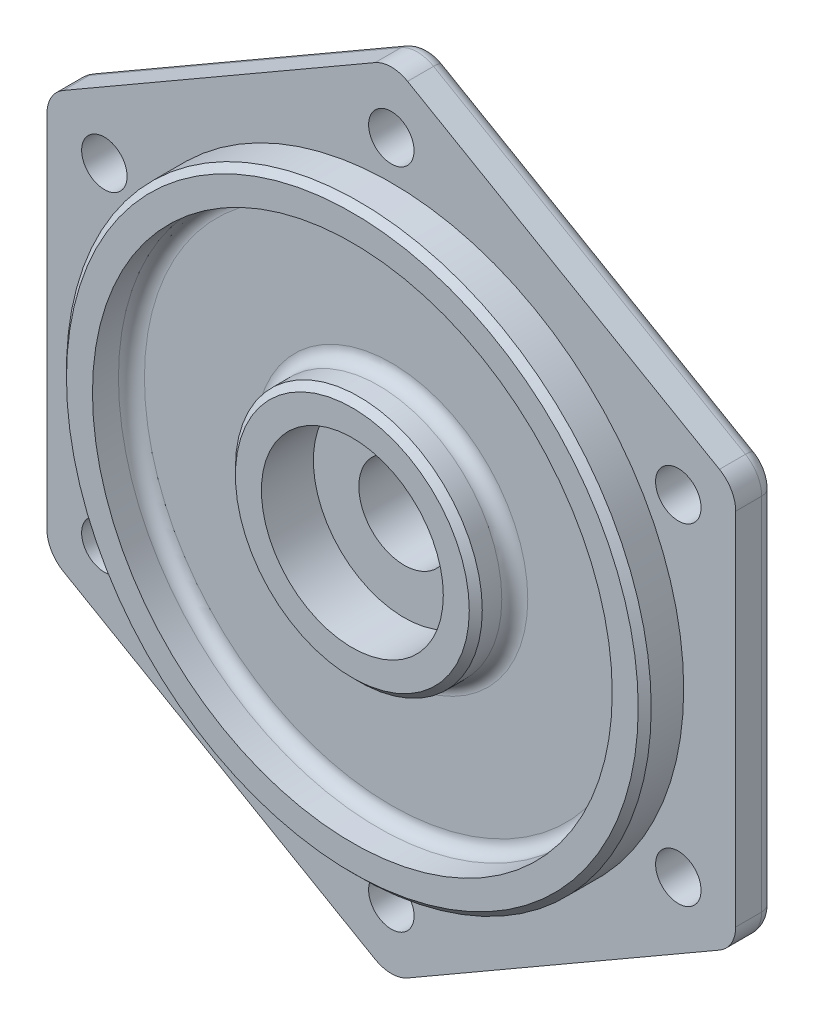
SolidWorks part; units mm, degrees
ref_plane "Front Plane" through (0, 0, 0) normal (0, 0, 1) x (1, 0, 0)
ref_plane "Top Plane" through (0, 0, 0) normal (0, 1, 0) x (1, 0, 0)
ref_plane "Right Plane" through (0, 0, 0) normal (1, 0, 0) x (0, 0, -1)
sketch "Sketch1" plane through (0, 0, 0) normal (0, 0, 1) x (1, 0, 0)
  line L1 (0, 61.1991) -> (-53, 30.5996)
  line L2 (-53, 30.5996) -> (-53, -30.5996)
  line L3 (-53, -30.5996) -> (0, -61.1991)
  line L4 (0, -61.1991) -> (53, -30.5996)
  line L5 (53, -30.5996) -> (53, 30.5996)
  line L6 (53, 30.5996) -> (0, 61.1991)
  circle A0 centre (0, 0) radius 53 construction
  point P1 (0, 0)
  dimension "D1" = 106
extrude "Boss-Extrude1" add sketch "Sketch1" against normal blind 6
sketch "Sketch2" plane through (0, 0, -6) normal (0, 0, -1) x (-1, 0, 0)
  circle A0 centre (0, 0) radius 23
  dimension "D1" = 46
extrude "Boss-Extrude2" add sketch "Sketch2" along normal blind 4
sketch "Sketch4" plane through (0, 0, 0) normal (0, 0, 1) x (1, 0, 0)
  circle A0 centre (0, 0) radius 45
  dimension "D1" = 90
extrude "Boss-Extrude3" add sketch "Sketch4" along normal blind 6
sketch "Sketch5" plane through (0, 0, 6) normal (0, 0, 1) x (1, 0, 0)
  circle A0 centre (0, 0) radius 40
  dimension "D1" = 80
extrude "Cut-Extrude1" cut sketch "Sketch5" against normal blind 6
sketch "Sketch6" plane through (0, 0, 0) normal (0, 0, 1) x (1, 0, 0)
  circle A0 centre (0, 0) radius 19
  dimension "D1" = 38
extrude "Boss-Extrude4" add sketch "Sketch6" along normal blind 6
sketch "Sketch7" plane through (0, 0, 6) normal (0, 0, 1) x (1, 0, 0)
  circle A0 centre (0, 0) radius 14
  dimension "D1" = 28
extrude "Cut-Extrude2" cut sketch "Sketch7" against normal blind 8
sketch "Sketch8" plane through (0, 0, -10) normal (0, 0, -1) x (-1, 0, 0)
  circle A0 centre (0, 0) radius 7
  dimension "D1" = 14
extrude "Cut-Extrude3" cut sketch "Sketch8" against normal through all
sketch "Sketch9" plane through (0, 0, 0) normal (0, 0, 1) x (1, 0, 0)
  circle A0 centre (0, 0) radius 51 construction
  circle A1 centre (0, 51) radius 3.5
  circle A2 centre (44.1673, 25.5) radius 3.5
  circle A3 centre (44.1673, -25.5) radius 3.5
  circle A4 centre (0, -51) radius 3.5
  circle A5 centre (-44.1673, -25.5) radius 3.5
  circle A6 centre (-44.1673, 25.5) radius 3.5
  point P5 (0, 0)
  point P7 (0, 0)
  point P18 (0, 0)
  point P19 (0, 0)
  dimension "D1" = 102
  dimension "D2" = 7
  dimension "D3" = 6
extrude "Cut-Extrude4" cut sketch "Sketch9" against normal through all both and the other way through all
fillet "Fillet1" radius 5 6 edges at (0, 61.1991, -3) (-53, -30.5996, -3) (0, -61.1991, -3) (53, -30.5996, -3) (53, 30.5996, -3) (-53, 30.5996, -3)
fillet "Fillet2" radius 4 1 edges at (-23, 0, -6)
fillet "Fillet3" radius 2 14 edges at (-52.3301, 30.2128, -6) (-26.5, 45.8993, -6) (0, 60.4256, -6) (26.5, 45.8993, -6) (52.3301, 30.2128, -6) (53, 0, -6) (52.3301, -30.2128, -6) (26.5, -45.8993, -6) (0, -60.4256, -6) (-26.5, -45.8993, -6) (-52.3301, -30.2128, -6) (-53, 0, -6) (40, 0, 0) (19, 0, 0)
chamfer "Chamfer1" distance 1 angle 45 2 edges at (45, 0, 6) (19, 0, 6)
